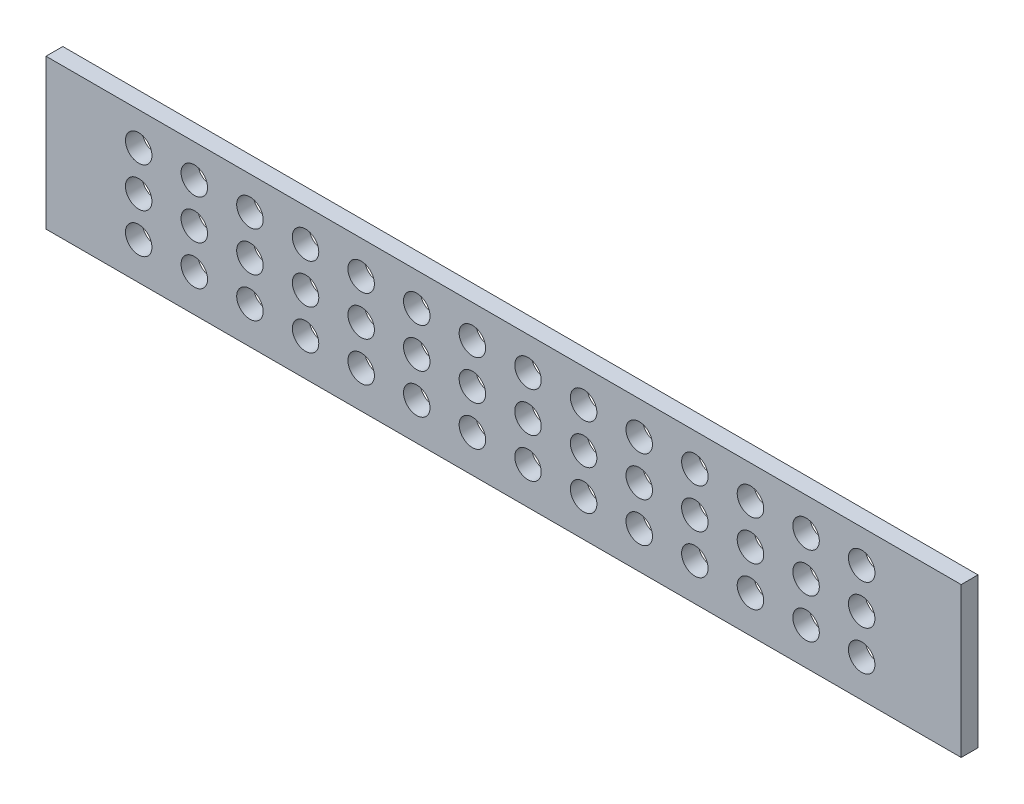
SolidWorks part; units mm, degrees
material "Custom Plastic"
ref_plane "X-Y Datum" through (0, 0, 0) normal (0, 0, 1) x (1, 0, 0)
ref_plane "X-Z Datum" through (0, 0, 0) normal (0, 1, 0) x (1, 0, 0)
ref_plane "Y-Z Datum" through (0, 0, 0) normal (1, 0, 0) x (0, 0, -1)
sketch "Sketch1" plane through (0, 0, 0) normal (0, 0, 1) x (1, 0, 0)
  line L1 (-172.785, -28.275) -> (172.785, -28.275)
  line L2 (-172.785, -28.275) -> (-172.785, 28.275)
  line L3 (-172.785, 28.275) -> (172.785, 28.275)
  line L4 (172.785, -28.275) -> (172.785, 28.275)
  line L5 (-172.785, -28.275) -> (172.785, 28.275) construction
  line L6 (-172.785, 28.275) -> (172.785, -28.275) construction
  point P0 (0, 0)
  dimension "D1" = 345.57
  dimension "D2" = 56.55
extrude "Boss-Extrude1" add sketch "Sketch1" along normal blind 6.35
sketch "Sketch2" plane through (0, 0, 6.35) normal (0, 0, 1) x (1, 0, 0)
  line L0 (172.785, -28.275) -> (172.785, 28.275) construction
  line L1 (-172.785, 28.275) -> (-172.785, -28.275) construction
  line L2 (-172.785, -28.275) -> (172.785, -28.275) construction
  line L3 (172.785, 28.275) -> (-172.785, 28.275) construction
  line L9 (-142.785, 20.775) -> (142.785, 20.775)
  line L10 (-142.785, 20.775) -> (-142.785, -20.775)
  line L11 (-142.785, -20.775) -> (142.785, -20.775)
  line L12 (142.785, 20.775) -> (142.785, -20.775)
  circle A0 centre (-137.785, 15.775) radius 5
  dimension "D3" = 10
  dimension "D1" = 30
  dimension "D2" = 7.5
  dimension "D4" = 30
  dimension "D5" = 7.5
extrude "Cut-Extrude1" cut sketch "Sketch2" against normal blind 10 contours A0 region at (-137.785, 15.775, 6.35)
pattern_linear "LPattern1" count 14 spacing 21 along (1, 0, 0) count 3 spacing 15 along (0, -1, 0) of "Cut-Extrude1"
